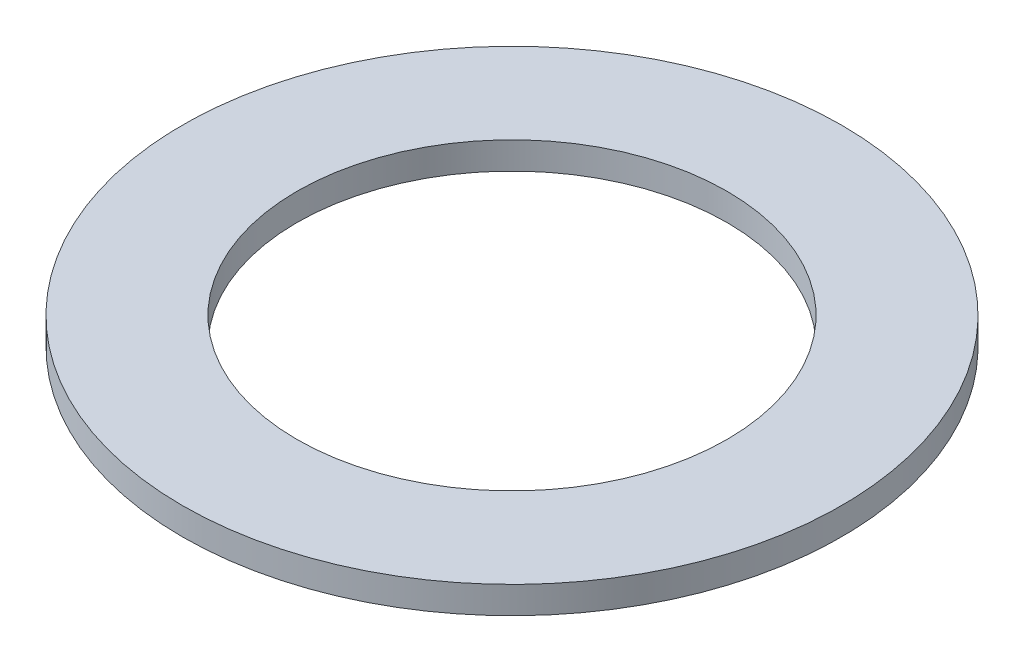
SolidWorks part; units mm, degrees
material "1060 Alloy"
ref_plane "Front Plane" through (0, 0, 0) normal (0, 0, 1) x (1, 0, 0)
ref_plane "Top Plane" through (0, 0, 0) normal (0, 1, 0) x (1, 0, 0)
ref_plane "Right Plane" through (0, 0, 0) normal (1, 0, 0) x (0, 0, -1)
sketch "Sketch1" plane through (0, 0, 0) normal (0, 1, 0) x (1, 0, 0)
  circle A0 centre (0, 0) radius 14.5
  circle A1 centre (0, 0) radius 22.225
  dimension "D1" = 29
  dimension "D2" = 44.45
extrude "Boss-Extrude1" add sketch "Sketch1" along normal blind 1.8288
